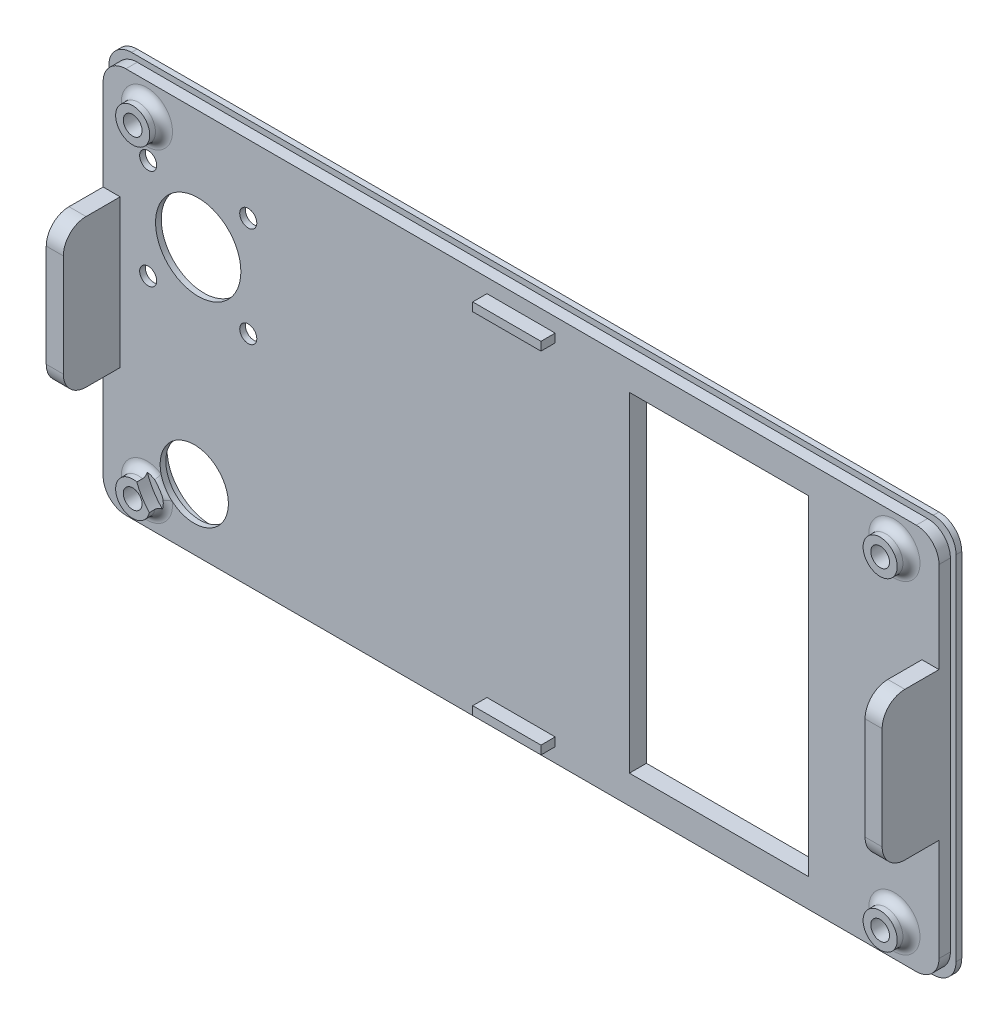
SolidWorks part; units mm, degrees
material "ПК/АБС"
ref_plane "Спереди" through (0, 0, 0) normal (0, 0, 1) x (1, 0, 0)
ref_plane "Сверху" through (0, 0, 0) normal (0, 1, 0) x (1, 0, 0)
ref_plane "Справа" through (0, 0, 0) normal (1, 0, 0) x (0, 0, -1)
sketch "Эскиз1" plane through (0, 0, 0) normal (0, 0, 1) x (1, 0, 0)
  line L1 (74.5, -35) -> (-74.5, -35)
  line L2 (74.5, -35) -> (74.5, 35)
  line L3 (74.5, 35) -> (-74.5, 35)
  line L4 (-74.5, -35) -> (-74.5, 35)
  line L5 (74.5, -35) -> (-74.5, 35) construction
  line L6 (74.5, 35) -> (-74.5, -35) construction
  point P0 (0, 0)
  dimension "D1" = 149
  dimension "D2" = 70
extrude "Бобышка-Вытянуть1" add sketch "Эскиз1" along normal blind 1
sketch "Эскиз2" plane through (0, 0, 1) normal (0, 0, 1) x (1, 0, 0)
  line L1 (73.5, -34) -> (-73.5, -34)
  line L2 (73.5, -34) -> (73.5, 34)
  line L3 (73.5, 34) -> (-73.5, 34)
  line L4 (-73.5, -34) -> (-73.5, 34)
  line L5 (73.5, -34) -> (-73.5, 34) construction
  line L6 (73.5, 34) -> (-73.5, -34) construction
  point P0 (0, 0)
  dimension "D1" = 147
  dimension "D2" = 68
extrude "Бобышка-Вытянуть2" add sketch "Эскиз2" along normal blind 2
fillet "Скругление1" radius 4 8 edges at (74.5, -35, 0.5) (73.5, -34, 2) (74.5, 35, 0.5) (73.5, 34, 2) (-74.5, -35, 0.5) (-73.5, -34, 2) (-74.5, 35, 0.5) (-73.5, 34, 2)
sketch "Эскиз3" plane through (0, 0, 3) normal (0, 0, 1) x (1, 0, 0)
  line L6 (-73.5, 30) -> (-73.5, -30) construction
  line L7 (-73.5, 14) -> (-70.5, 14)
  line L8 (-73.5, 14) -> (-73.5, -12)
  line L9 (-73.5, -12) -> (-70.5, -12)
  line L10 (-70.5, 14) -> (-70.5, -12)
  line L11 (73.5, 14) -> (70.5, 14)
  line L12 (73.5, 14) -> (73.5, -12)
  line L13 (73.5, -12) -> (70.5, -12)
  line L14 (70.5, 14) -> (70.5, -12)
  dimension "D1" = 3
extrude "Бобышка-Вытянуть3" add sketch "Эскиз3" along normal blind 10
fillet "Скругление2" radius 4 4 edges at (72, -12, 13) (72, 14, 13) (-72, -12, 13) (-72, 14, 13)
sketch "Эскиз4" plane through (0, 0, 3) normal (0, 0, 1) x (1, 0, 0)
  line L0 (0, 31.5) -> (0, -31.5) construction
  line L1 (68.775, -31.5) -> (-68.775, -31.5) construction
  line L2 (68.775, -31.5) -> (68.775, 31.5) construction
  line L3 (68.775, 31.5) -> (-68.775, 31.5) construction
  line L4 (-68.775, -31.5) -> (-68.775, 31.5) construction
  line L5 (68.775, -31.5) -> (-68.775, 31.5) construction
  line L6 (68.775, 31.5) -> (-68.775, -31.5) construction
  line L7 (-68.775, 0) -> (68.775, 0) construction
  line L8 (-6, 31.5) -> (6, 31.5)
  line L9 (-6, 31.5) -> (-6, 30)
  line L10 (-6, 30) -> (6, 30)
  line L11 (6, 31.5) -> (6, 30)
  line L12 (-6, -31.5) -> (-6, -30)
  line L13 (-6, -31.5) -> (6, -31.5)
  line L14 (6, -31.5) -> (6, -30)
  line L15 (-6, -30) -> (6, -30)
  circle A0 centre (-65.8, -28.375) radius 3
  circle A1 centre (-65.8, 28.5) radius 3
  circle A2 centre (65.65, -28.375) radius 3
  circle A3 centre (65.65, 28.5) radius 3
  point P0 (0, 0)
  point P20 (-6, 30.75)
  dimension "D3" = 6
  dimension "D4" = 3.125
  dimension "D5" = 2.975
  dimension "D6" = 56.875
  dimension "D7" = 6
  dimension "D8" = 131.45
  dimension "D9" = 6
  dimension "D10" = 6
  dimension "D1" = 137.55
  dimension "D2" = 63
  dimension "D11" = 6
  dimension "D12" = 6
  dimension "D13" = 1.5
extrude "Бобышка-Вытянуть4" add sketch "Эскиз4" along normal blind 2.5
sketch "Эскиз5" plane through (0, 0, 3) normal (0, 0, 1) x (1, 0, 0)
  circle A0 centre (-57.475, -23.225) radius 6
  circle A1 centre (-65.8, -28.375) radius 3 construction
  circle A2 centre (-65.8, -28.375) radius 3 construction
  dimension "D1" = 8.325
  dimension "D2" = 5.15
  dimension "D3" = 12
extrude "Вырез-Вытянуть1" cut sketch "Эскиз5" against normal through all
sketch "Эскиз6" plane through (0, 0, 0) normal (0, 0, -1) x (-1, 0, 0)
  circle A0 centre (57.475, -23.225) radius 7.8
  dimension "D1" = 15.6
extrude "Вырез-Вытянуть2" cut sketch "Эскиз6" against normal blind 2
sketch "Эскиз7" plane through (0, 0, 5.5) normal (0, 0, 1) x (1, 0, 0)
  circle A0 centre (-65.8, -28.375) radius 1.65
  circle A1 centre (-65.8, 28.5) radius 1.65
  circle A2 centre (65.65, 28.5) radius 1.65
  circle A3 centre (65.65, -28.375) radius 1.65
  dimension "D1" = 3.3
  dimension "D2" = 3.3
  dimension "D3" = 3.3
  dimension "D4" = 3.3
extrude "Вырез-Вытянуть3" cut sketch "Эскиз7" against normal blind 4
sketch "Эскиз8" plane through (0, 0, 3) normal (0, 0, 1) x (1, 0, 0)
  circle A0 centre (-56.775, 13.205) radius 7.5
  circle A1 centre (-65.8, -28.375) radius 1.65 construction
  circle A2 centre (-65.8, -28.375) radius 1.65 construction
  dimension "D1" = 41.58
  dimension "D2" = 9.025
  dimension "D3" = 15
extrude "Вырез-Вытянуть4" cut sketch "Эскиз8" against normal through all
sketch "Эскиз9" plane through (0, 0, 0) normal (0, 0, -1) x (-1, 0, 0)
  line L1 (69.375, 0.605) -> (44.175, 0.605)
  line L2 (69.375, 0.605) -> (69.375, 25.805)
  line L3 (69.375, 25.805) -> (44.175, 25.805)
  line L4 (44.175, 0.605) -> (44.175, 25.805)
  line L5 (69.375, 0.605) -> (44.175, 25.805) construction
  line L6 (69.375, 25.805) -> (44.175, 0.605) construction
  point P0 (56.775, 13.205)
  dimension "D1" = 25.2
  dimension "D2" = 25.2
extrude "Вырез-Вытянуть5" cut sketch "Эскиз9" against normal blind 2
sketch "Эскиз10" plane through (0, 0, 2) normal (0, 0, -1) x (-1, 0, 0)
  line L0 (56.775, 25.805) -> (56.775, 0.605) construction
  line L1 (69.375, 25.805) -> (44.175, 25.805) construction
  line L2 (44.175, 0.605) -> (69.375, 0.605) construction
  line L3 (44.175, 13.205) -> (69.375, 13.205) construction
  line L4 (44.175, 25.805) -> (44.175, 0.605) construction
  line L5 (69.375, 0.605) -> (69.375, 25.805) construction
  circle A0 centre (47.975, 4.405) radius 1.5
  circle A1 centre (65.575, 4.405) radius 1.5
  circle A2 centre (65.575, 22.005) radius 1.5
  circle A3 centre (47.975, 22.005) radius 1.5
  dimension "D1" = 8.8
  dimension "D2" = 8.8
  dimension "D3" = 3
extrude "Вырез-Вытянуть6" cut sketch "Эскиз10" against normal through all
sketch "Эскиз11" plane through (0, 0, 3) normal (0, 0, 1) x (1, 0, 0)
  line L0 (29.05, -28.428) -> (40.55, -17.428) construction
  line L1 (29.05, 22.65) -> (40.55, 22.65) construction
  line L2 (29.05, 22.65) -> (29.05, 11.65) construction
  line L3 (29.05, 11.65) -> (40.55, 11.65) construction
  line L4 (40.55, 22.65) -> (40.55, 11.65) construction
  line L5 (29.05, 22.65) -> (40.55, 11.65) construction
  line L6 (29.05, 11.65) -> (40.55, 22.65) construction
  line L11 (29.05, -17.428) -> (40.55, -17.428) construction
  line L12 (29.05, -17.428) -> (29.05, -28.428) construction
  line L13 (29.05, -28.428) -> (40.55, -28.428) construction
  line L14 (40.55, -17.428) -> (40.55, -28.428) construction
  line L15 (29.05, -17.428) -> (40.55, -28.428) construction
  line L16 (-69.5, -34) -> (69.5, -34) construction
  line L17 (19.05, 29) -> (50.55, 29)
  line L18 (19.05, 29) -> (19.05, -29)
  line L19 (19.05, -29) -> (50.55, -29)
  line L20 (50.55, 29) -> (50.55, -29)
  line L21 (69.5, 34) -> (-69.5, 34) construction
  circle A0 centre (65.65, 28.5) radius 1.65 construction
  circle A1 centre (65.65, 28.5) radius 3 construction
  circle A2 centre (65.65, -28.375) radius 3 construction
  point P0 (34.8, 17.15)
  point P15 (34.8, -22.928)
  dimension "D3" = 30.85
  dimension "D4" = 11.35
  dimension "D5" = 11
  dimension "D6" = 5.447
  dimension "D8" = 5
  dimension "D1" = 11.5
  dimension "D2" = 11
  dimension "D7" = 5
  dimension "D9" = 10
  dimension "D10" = 10
extrude "Вырез-Вытянуть7" cut sketch "Эскиз11" against normal through all
fillet "Скругление3" radius 1.5 4 edges at (-62.8, -28.375, 3) (68.65, -28.375, 3) (68.65, 28.5, 3) (-62.8, 28.5, 3)
fillet "Скругление4" radius 2 4 edges at (-44.175, 0.605, 1) (-69.375, 0.605, 1) (-69.375, 25.805, 1) (-44.175, 25.805, 1)
sketch "Эскиз15" plane through (0, 0, 5.5) normal (0, 0, 1) x (1, 0, 0)
  arc A0 (-62.823, -28.0043) -> (-64.1392, -25.8767) centre (-65.8, -28.375) ccw construction
  ellipse E0 centre (-63.2487, -26.7967) end of major axis (-65.1192, -23.773) minor radius 1.0532
extrude "Вырез-Вытянуть9" cut sketch "Эскиз15" against normal blind 2
